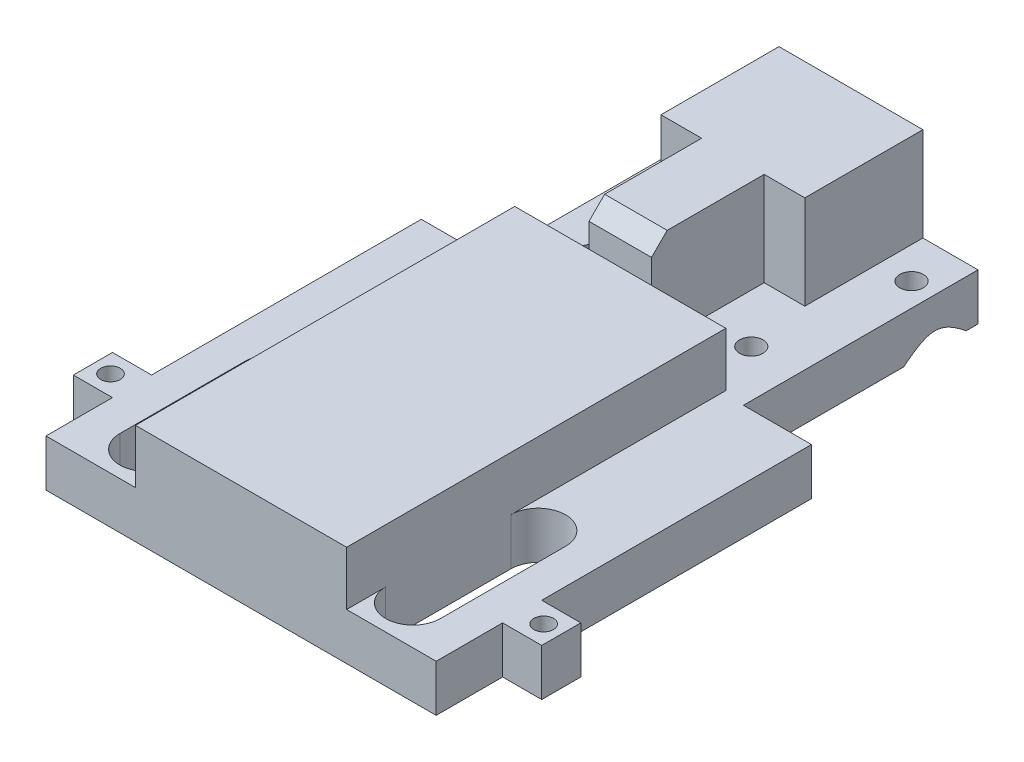
SolidWorks part; units mm, degrees
ref_plane "前视基准面" through (0, 0, 0) normal (0, 0, 1) x (1, 0, 0)
ref_plane "上视基准面" through (0, 0, 0) normal (0, 1, 0) x (1, 0, 0)
ref_plane "右视基准面" through (0, 0, 0) normal (1, 0, 0) x (0, 0, -1)
sketch "草图1" plane through (0, 0, 0) normal (0, 1, 0) x (1, 0, 0)
  line L0 (0, 40) -> (0, 38.5) construction
  line L1 (-25.45, -32) -> (-25.45, -28)
  line L2 (-25.45, -3.5) -> (-25.45, 0.5)
  line L3 (-25.45, -40) -> (25.45, -40)
  line L4 (25.45, -28) -> (25.45, -32)
  line L5 (25.45, -3.5) -> (25.45, 0.5)
  line L8 (-25.45, 8.5) -> (-16.25, 8.5) construction
  line L10 (-25.45, 8.5) -> (-16.25, 8.5)
  line L11 (-25.45, 8.5) -> (-25.45, 0.5)
  line L15 (25.45, -3.5) -> (25.45, -28)
  line L20 (-25.45, -3.5) -> (-25.45, -28)
  line L21 (25.45, 8.5) -> (25.45, 0.5)
  line L30 (-25.45, -32) -> (-25.45, -40)
  line L31 (25.45, -32) -> (25.45, -40)
  line L32 (16.25, 8.5) -> (25.45, 8.5)
  line L33 (-16.25, 38.5) -> (16.25, 38.5)
  line L34 (-16.25, 38.5) -> (-16.25, 8.5)
  line L35 (16.25, 8.5) -> (25.45, 8.5) construction
  line L36 (16.25, 38.5) -> (16.25, 8.5)
  point P0 (0, 0)
  dimension "D2" = 25.45
  dimension "D3" = 50.9
  dimension "D4" = 48.5
  dimension "D5" = 9.2
  dimension "D6" = 9.2
  dimension "D7" = 78.5
  dimension "D10" = 30
  dimension "D11" = 32.5
  dimension "D18" = 40
extrude "凸台-拉伸1" add sketch "草图1" along normal blind 6
sketch "草图2" plane through (0, 6, 0) normal (0, 1, 0) x (1, 0, 0)
  line L0 (-16.25, 8.5) -> (16.25, 8.5) construction
  line L1 (-16.25, 38.5) -> (-16.25, 8.5) construction
  line L3 (-4, 22.9) -> (-4, 8.5)
  line L4 (-4, 8.5) -> (4, 8.5)
  line L5 (4, 22.9) -> (4, 8.5)
  line L6 (16.25, 8.5) -> (16.25, 38.5) construction
  line L7 (4, 22.9) -> (9.2, 22.9)
  line L8 (9.2, 22.9) -> (9.2, 38.5)
  line L9 (16.25, 38.5) -> (-16.25, 38.5) construction
  line L10 (9.2, 38.5) -> (-9.2, 38.5)
  line L11 (-9.2, 38.5) -> (-9.2, 22.9)
  line L12 (-9.2, 22.9) -> (-4, 22.9)
  dimension "D1" = 8
  dimension "D2" = 12.25
  dimension "D3" = 12.25
  dimension "D4" = 14.4
  dimension "D5" = 5.2
  dimension "D6" = 5.2
  dimension "D7" = 14.4
extrude "凸台-拉伸2" add sketch "草图2" along normal blind 12
sketch "草图3" plane through (0, 0, 0) normal (0, -1, 0) x (1, 0, 0)
  line L1 (16.25, -38.5) -> (-16.25, -38.5) construction
  line L11 (16.25, -8.5) -> (16.25, -38.5) construction
  line L12 (0, 0) -> (0, -38.5) construction
  line L13 (25.45, -8.5) -> (16.25, -8.5) construction
  line L14 (17, 19) -> (17, 35) construction
  line L15 (13.5, 19) -> (13.5, 35)
  line L16 (20.5, 19) -> (20.5, 35)
  line L19 (-25.45, 40) -> (25.45, 40) construction
  line L20 (-17, 19) -> (-17, 35) construction
  line L21 (-13.5, 19) -> (-13.5, 35)
  line L22 (-20.5, 19) -> (-20.5, 35)
  circle A4 centre (13.25, -32.5) radius 1.5
  circle A5 centre (10.25, -15) radius 1.5
  circle A6 centre (-13.25, -32.5) radius 1.5
  circle A7 centre (-10.25, -15) radius 1.5
  arc A8 (13.5, 19) -> (20.5, 19) centre (17, 19) ccw
  arc A9 (20.5, 35) -> (13.5, 35) centre (17, 35) ccw
  arc A10 (-13.5, 19) -> (-20.5, 19) centre (-17, 19) cw
  arc A11 (-20.5, 35) -> (-13.5, 35) centre (-17, 35) cw
  point P43 (17, 27)
  point P49 (-17, 27)
  dimension "D15" = 3
  dimension "D16" = 6
  dimension "D17" = 3
  dimension "D20" = 3.5
  dimension "D3" = 17
  dimension "D13" = 6
  dimension "D14" = 3
  dimension "D18" = 6.5
  dimension "D19" = 16
  dimension "D22" = 13
extrude "切除-拉伸1" cut sketch "草图3" against normal up to next
chamfer "倒角1" distance 2 angle 45 1 edges at (0, 18, -8.5)
sketch "草图4" plane through (0, 6, 0) normal (0, 1, 0) x (1, 0, 0)
  line L0 (0, -40) -> (0, 8.5) construction
  line L1 (-25.45, -40) -> (25.45, -40) construction
  line L2 (-4, 8.5) -> (4, 8.5) construction
  line L4 (-13.5, 8.5) -> (13.5, 8.5)
  line L5 (-13.5, 8.5) -> (-13.5, -40)
  line L6 (-13.5, -40) -> (13.5, -40)
  line L7 (13.5, 8.5) -> (13.5, -40)
  line L8 (-13.5, 8.5) -> (13.5, -40) construction
  line L9 (-13.5, -40) -> (13.5, 8.5) construction
  point P6 (0, -15.75)
  dimension "D1" = 13.5
extrude "凸台-拉伸3" add sketch "草图4" along normal blind 6.9
sketch "草图5" plane through (0, 0, 0) normal (0, -1, 0) x (1, 0, 0)
  line L0 (24.95, 40) -> (24.95, -8)
  line L1 (-25.45, 40) -> (25.45, 40) construction
  line L2 (24.95, -8) -> (16.25, -8)
  line L3 (16.25, -8) -> (16.25, -8.5)
  line L4 (16.25, -8.5) -> (25.45, -8.5)
  line L5 (25.45, -8.5) -> (25.45, 40)
  line L6 (25.45, 40) -> (24.95, 40)
  line L7 (-16.25, -8.5) -> (-25.45, -8.5)
  line L8 (-25.45, -8.5) -> (-25.45, 40)
  line L9 (-25.45, 40) -> (-24.95, 40)
  line L10 (-24.95, 40) -> (-24.95, -8)
  line L11 (-24.95, -8) -> (-16.25, -8)
  line L12 (-16.25, -8) -> (-16.25, -8.5)
  line L13 (16.25, -8.5) -> (16.25, -38.5) construction
  line L14 (16.25, -38) -> (-16.25, -38)
  line L15 (16.25, -38) -> (16.25, -38.5)
  line L16 (16.25, -38.5) -> (-16.25, -38.5)
  line L17 (-16.25, -38) -> (-16.25, -38.5)
  line L18 (16.25, -38.5) -> (-16.25, -38.5) construction
  dimension "D1" = 0.5
  dimension "D2" = 0.5
  dimension "D3" = 0.5
  dimension "D4" = 0.5
  dimension "D5" = 0.5
extrude "切除-拉伸2" cut sketch "草图5" against normal through all
sketch "草图6" plane through (0, 0, 0) normal (0, -1, 0) x (1, 0, 0)
  line L0 (-24.95, -8) -> (-24.95, 40) construction
  line L1 (-29.95, 31.5) -> (-24.95, 31.5)
  line L2 (-29.95, 31.5) -> (-29.95, 26.5)
  line L3 (-29.95, 26.5) -> (-24.95, 26.5)
  line L4 (-24.95, 31.5) -> (-24.95, 26.5)
  line L5 (-29.95, 31.5) -> (-24.95, 26.5) construction
  line L6 (-29.95, 26.5) -> (-24.95, 31.5) construction
  line L7 (-24.95, 40) -> (24.95, 40) construction
  line L8 (0, 40) -> (0, -38) construction
  line L9 (16.25, -38) -> (-16.25, -38) construction
  line L10 (29.95, 26.5) -> (24.95, 31.5) construction
  line L11 (29.95, 31.5) -> (24.95, 26.5) construction
  line L12 (24.95, 31.5) -> (24.95, 26.5)
  line L13 (29.95, 26.5) -> (24.95, 26.5)
  line L14 (29.95, 31.5) -> (29.95, 26.5)
  line L15 (29.95, 31.5) -> (24.95, 31.5)
  point P0 (-27.45, 29)
  point P17 (27.45, 29)
  dimension "D1" = 11
  dimension "D2" = 5
  dimension "D3" = 5
extrude "凸台-拉伸4" add sketch "草图6" against normal blind 6
sketch "草图9" plane through (0, 0, 0) normal (0, -1, 0) x (1, 0, 0)
  line L0 (-29.95, 31.5) -> (-29.95, 26.5) construction
  line L1 (-24.95, 31.5) -> (-29.95, 31.5) construction
  line L2 (29.95, 26.5) -> (29.95, 31.5) construction
  line L4 (29.95, 31.5) -> (24.95, 31.5) construction
  circle A0 centre (-27.7, 29) radius 1.25
  circle A1 centre (27.7, 29) radius 1.25
  dimension "D3" = 2.5
  dimension "D6" = 2.5
  dimension "D1" = 2.25
  dimension "D2" = 2.5
  dimension "D4" = 2.25
  dimension "D5" = 2.5
extrude "切除-拉伸5" cut sketch "草图9" against normal through all
sketch "草图10" plane through (0, 0, 0) normal (0, -1, 0) x (1, 0, 0)
  circle A0 centre (27.7, 29) radius 2
  circle A1 centre (-27.7, 29) radius 2
  dimension "D1" = 4
  dimension "D2" = 4
extrude "切除-拉伸6" cut sketch "草图10" against normal offset from surface (4 mm away) 2 up to face at (27.7, 6, 30.25)
chamfer "倒角3" distance 3.5 angle 45 4 edges at (-13.25, 0, -31) (13.25, 0, -34) (10.25, 0, -16.5) (-10.25, 0, -13.5)
